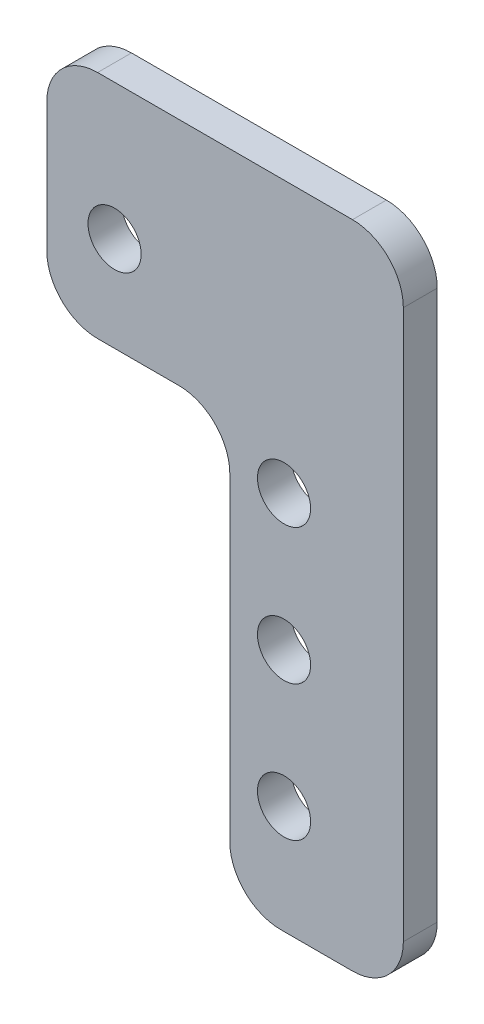
SolidWorks part; units mm, degrees
material "6061-T6 (SS)"
ref_plane "Front Plane" through (0, 0, 0) normal (0, 0, 1) x (1, 0, 0)
ref_plane "Top Plane" through (0, 0, 0) normal (0, 1, 0) x (1, 0, 0)
ref_plane "Right Plane" through (0, 0, 0) normal (1, 0, 0) x (0, 0, -1)
sketch "Sketch1" plane through (0, 0, 0) normal (0, 0, 1) x (1, 0, 0)
  line L6 (28.575, -2.54) -> (61.976, -2.54)
  line L7 (61.976, -2.54) -> (61.976, -63.5)
  line L8 (61.976, -63.5) -> (45.72, -63.5)
  line L9 (45.72, -63.5) -> (45.72, -24.13)
  line L10 (45.72, -24.13) -> (28.575, -24.13)
  line L12 (28.575, -2.54) -> (28.575, -24.13)
  line L18 (0, 0) -> (69.85, 0) construction
  line L19 (0, 0) -> (0, -63.5) construction
  line L20 (0, -63.5) -> (69.85, -63.5) construction
  line L21 (69.85, 0) -> (69.85, -63.5) construction
  circle A0 centre (50.8, -15.24) radius 2.4892 construction
  circle A1 centre (50.8, -27.94) radius 2.4892
  circle A2 centre (50.8, -40.64) radius 2.4892
  circle A3 centre (50.8, -53.34) radius 2.4892
  circle A4 centre (34.925, -15.24) radius 2.4892
  dimension "D4" = 12.7
  dimension "D6" = 4.9784
  dimension "D10" = 24.13
  dimension "D12" = 12.7
  dimension "D13" = 27.051
  dimension "D14" = 6.35
  dimension "D9" = 16.256
  dimension "D11" = 19.05
  dimension "D2" = 63.5
  dimension "D5" = 69.85
  dimension "D7" = 24.13
  dimension "D8" = 2.54
  dimension "D3" = 4
extrude "Boss-Extrude1" add sketch "Sketch1" along normal blind 3.175
fillet "Fillet1" radius 4.7625 6 edges at (61.976, -63.5, 1.5875) (45.72, -63.5, 1.5875) (45.72, -24.13, 1.5875) (28.575, -24.13, 1.5875) (28.575, -2.54, 1.5875) (61.976, -2.54, 1.5875)
